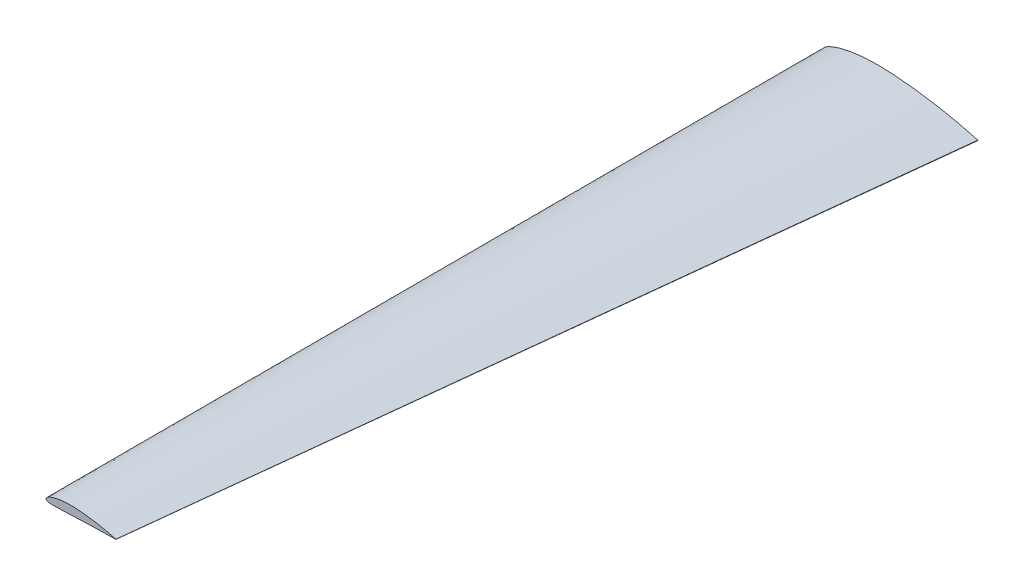
SolidWorks part; units mm, degrees
ref_plane "Front Plane" through (0, 0, 0) normal (0, 0, 1) x (1, 0, 0)
ref_plane "Top Plane" through (0, 0, 0) normal (0, 1, 0) x (1, 0, 0)
ref_plane "Right Plane" through (0, 0, 0) normal (1, 0, 0) x (0, 0, -1)
curve "Curve1"
  spline degree 3 poles (25.4, 0.033, 0) (24.9771, 0.1481, 0) (24.1334, 0.3778, 0) (22.4431, 0.7955, 0) (20.3293, 1.2569, 0) (17.7869, 1.7118, 0) (15.2464, 2.0846, 0) (12.7045, 2.3505, 0) (10.1628, 2.5164, 0) (8.041, 2.5181, 0) (6.3469, 2.4009, 0) (5.0745, 2.2465, 0) (3.7995, 2.0188, 0) (2.7428, 1.745, 0) (1.8961, 1.4685, 0) (1.2577, 1.2074, 0) (0.7129, 0.9251, 0) (0.2401, 0.5874, 0) (-0.1715, 0.0442, 0) (0.2727, -0.3711, 0) (0.7261, -0.5342, 0) (1.266, -0.6443, 0) (1.9036, -0.7002, 0) (2.7513, -0.7398, 0) (3.8103, -0.7368, 0) (5.0806, -0.7013, 0) (6.3499, -0.6336, 0) (8.0433, -0.5544, 0) (10.1596, -0.4528, 0) (12.7001, -0.3574, 0) (15.2397, -0.2514, 0) (17.7796, -0.1611, 0) (20.3198, -0.0947, 0) (22.4366, -0.061, 0) (24.13, -0.0388, 0) (24.9767, -0.035, 0) (25.4, -0.033, 0) knots 0 0 0 0 0.025305 0.050488 0.10052 0.150191 0.199587 0.24874 0.297716 0.346601 0.371103 0.395726 0.42057 0.445825 0.458702 0.47192 0.485786 0.493461 0.506863 0.516148 0.522766 0.535269 0.547551 0.559786 0.584229 0.608681 0.633151 0.657622 0.706558 0.755482 0.804406 0.85332 0.902221 0.951113 0.975557 1 1 1 1
sketch "Sketch1" plane through (0, 0, 0) normal (0, 0, 1) x (1, 0, 0)
  arc A0 (100.041, 0.1301) -> (100.041, -0.1301) centre (100.0005, 0) cw
  spline S1 degree 3 poles (100.041, 0.1301) (98.3753, 0.5835) (95.0521, 1.4881) (88.3947, 3.133) (80.0695, 4.9504) (70.0557, 6.7419) (60.0498, 8.2104) (50.0382, 9.2579) (40.0275, 9.9112) (31.6705, 9.9178) (24.9979, 9.4562) (19.9867, 8.8481) (14.9646, 7.9514) (10.803, 6.873) (7.4681, 5.7839) (4.9535, 4.7556) (2.8079, 3.6437) (0.9456, 2.3135) (-0.6757, 0.1743) (1.0742, -1.4618) (2.8598, -2.104) (4.9863, -2.5375) (7.4977, -2.7579) (10.8364, -2.9138) (15.0072, -2.9022) (20.0104, -2.7622) (25.01, -2.4956) (31.6794, -2.1837) (40.0148, -1.7834) (50.0208, -1.4075) (60.0235, -0.9901) (70.0273, -0.6346) (80.0318, -0.3732) (88.3693, -0.2404) (95.0388, -0.153) (98.3736, -0.1377) (100.041, -0.1301) knots 0 0 0 0 0.025305 0.050488 0.10052 0.150191 0.199587 0.24874 0.297716 0.346601 0.371103 0.395726 0.42057 0.445825 0.458702 0.47192 0.485786 0.493461 0.506863 0.516148 0.522766 0.535269 0.547551 0.559786 0.584229 0.608681 0.633151 0.657622 0.706558 0.755482 0.804406 0.85332 0.902221 0.951113 0.975557 1 1 1 1
ref_plane "Plane1" through (0, 0, 500) normal (0, 0, 1) x (1, 0, 0)
sketch "Sketch2" plane through (0, 0, 500) normal (0, 0, 1) x (1, 0, 0)
  arc A0 (45, 0.0585) -> (45, -0.0585) centre (44.9843, 0) cw
  spline S1 degree 3 poles (45, 0.0585) (44.2508, 0.2625) (42.7559, 0.6694) (39.7613, 1.4093) (36.0165, 2.2268) (31.5122, 3.0326) (27.0113, 3.6932) (22.508, 4.1644) (18.005, 4.4582) (14.2459, 4.4612) (11.2444, 4.2535) (8.9903, 3.98) (6.7313, 3.5767) (4.8594, 3.0916) (3.3593, 2.6017) (2.2282, 2.1392) (1.2631, 1.639) (0.4253, 1.0407) (-0.3039, 0.0784) (0.4832, -0.6575) (1.2864, -0.9464) (2.2429, -1.1414) (3.3726, -1.2405) (4.8744, -1.3107) (6.7505, -1.3054) (9.001, -1.2425) (11.2499, -1.1225) (14.2499, -0.9822) (17.9993, -0.8022) (22.5001, -0.6331) (26.9995, -0.4454) (31.4994, -0.2855) (35.9996, -0.1678) (39.7499, -0.1081) (42.7499, -0.0688) (44.25, -0.0619) (45, -0.0585) knots 0 0 0 0 0.025305 0.050488 0.10052 0.150191 0.199587 0.24874 0.297716 0.346601 0.371103 0.395726 0.42057 0.445825 0.458702 0.47192 0.485786 0.493461 0.506863 0.516148 0.522766 0.535269 0.547551 0.559786 0.584229 0.608681 0.633151 0.657622 0.706558 0.755482 0.804406 0.85332 0.902221 0.951113 0.975557 1 1 1 1
loft "Loft1" add profiles "Sketch2", "Sketch1" connector at (45, 0.0585, 500) connector at (100.041, 0.1301, 0)
